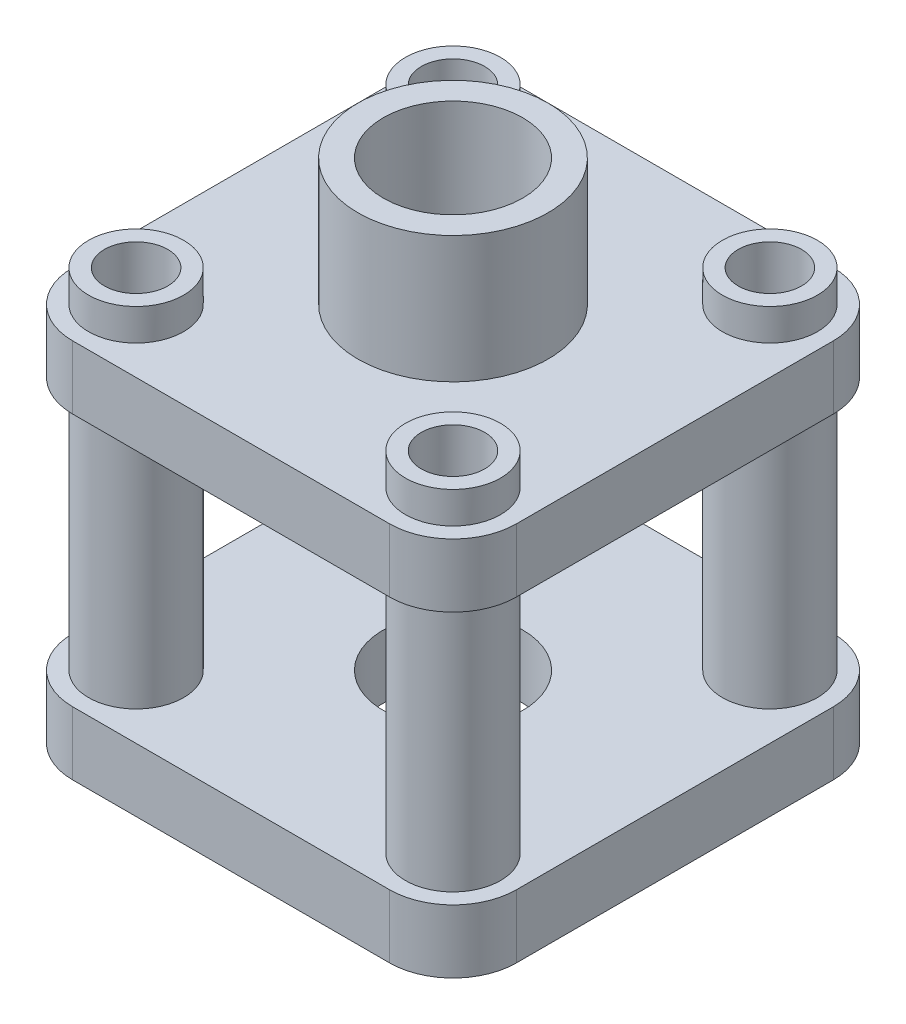
SolidWorks part; units mm, degrees
ref_plane "Front Plane" through (0, 0, 0) normal (0, 0, 1) x (1, 0, 0)
ref_plane "Top Plane" through (0, 0, 0) normal (0, 1, 0) x (1, 0, 0)
ref_plane "Right Plane" through (0, 0, 0) normal (1, 0, 0) x (0, 0, -1)
sketch "Sketch1" plane through (0, 0, 0) normal (0, 1, 0) x (1, 0, 0)
  line L0 (0, 0) -> (0, 42533.7281) construction
  line L1 (0, 0) -> (-42533.7281, 0) construction
  line L3 (-35, -35) -> (35, -35)
  line L4 (-35, -35) -> (-35, 35)
  line L5 (-35, 35) -> (35, 35)
  line L6 (35, -35) -> (35, 35)
  line L7 (-35, -35) -> (35, 35) construction
  line L8 (-35, 35) -> (35, -35) construction
  point P5 (0, 0)
  dimension "D1" = 70
  dimension "D2" = 70
extrude "Boss-Extrude1" add sketch "Sketch1" along normal blind 10
pattern_linear "LPattern2" count 2 spacing 50 along (0, -1, 0) of bodies 101
sketch "Sketch2" plane through (0, 10, 0) normal (0, 1, 0) x (1, 0, 0)
  line L0 (-35, 35) -> (35, -35) construction
  line L1 (35, 35) -> (-35, -35) construction
  line L2 (0, 35) -> (0, -35) construction
  line L3 (35, 35) -> (-35, 35) construction
  line L4 (-35, -35) -> (35, -35) construction
  line L5 (-35, 0) -> (35, 0) construction
  line L6 (-35, 35) -> (-35, -35) construction
  line L7 (35, -35) -> (35, 35) construction
  circle A0 centre (0, 0) radius 15
  circle A1 centre (0, 0) radius 11
  circle A2 centre (25, 25) radius 7.5
  circle A3 centre (25, 25) radius 5
  circle A4 centre (-25, 25) radius 5
  circle A5 centre (-25, 25) radius 7.5
  circle A6 centre (25, -25) radius 7.5
  circle A7 centre (25, -25) radius 5
  circle A8 centre (-25, -25) radius 7.5
  circle A9 centre (-25, -25) radius 5
  dimension "D1" = 30
  dimension "D2" = 22
  dimension "D3" = 15
  dimension "D4" = 10
  dimension "D5" = 25
  dimension "D6" = 25
extrude "Boss-Extrude2" add sketch "Sketch2" along normal blind 20 contours A0 A1 region at (-14.5757, 10, 0)
extrude "Boss-Extrude3" add sketch "Sketch2<3>" against normal blind 55 and the other way blind 5 contours A5 A4 | A2 A3 | A8 A9 | A6 A7 region at (17.7121, 10, -25) region at (-32.2879, 10, -25) region at (17.7121, 10, 25) region at (-32.2879, 10, 25)
sketch "Sketch2<3>" plane through (0, 10, 0) normal (0, 1, 0) x (1, 0, 0) same geometry as "Sketch2"
sketch "Sketch3" plane through (0, 10, 0) normal (0, 1, 0) x (1, 0, 0)
  line L0 (0, 35) -> (0, -35) construction
  line L1 (35, 35) -> (-35, 35) construction
  line L2 (-35, -35) -> (35, -35) construction
  line L3 (-35, 0) -> (35, 0) construction
  line L4 (-35, 35) -> (-35, -35) construction
  line L5 (35, -35) -> (35, 35) construction
  line L6 (-25, -20) -> (-25, -30) construction
  line L7 (-30, -25) -> (-20, -25) construction
  circle A0 centre (-25, -25) radius 5 construction
  circle A1 centre (-25, -25) radius 5 construction
  circle A2 centre (-25, -25) radius 5
  circle A3 centre (-25, 25) radius 5
  circle A4 centre (25, -25) radius 5
  circle A5 centre (25, 25) radius 5
  circle A6 centre (0, 0) radius 11
  dimension "D1" = 10
  dimension "D2" = 25
  dimension "D3" = 22
extrude "Cut-Extrude1" cut sketch "Sketch3" against normal blind 100
fillet "Fillet1" radius 10 8 edges at (35, -45, 35) (35, -45, -35) (-35, -45, -35) (-35, -45, 35) (-35, 5, 35) (-35, 5, -35) (35, 5, -35) (35, 5, 35)
